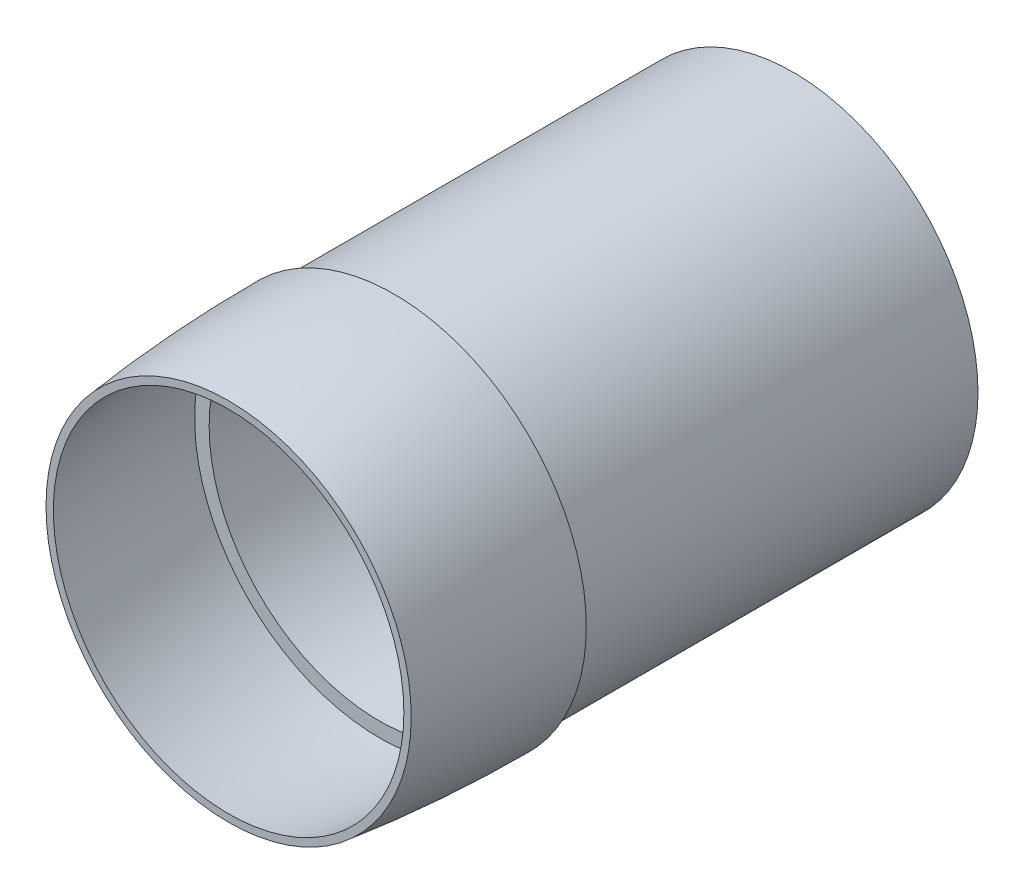
SolidWorks part; units mm, degrees
ref_plane "Front Plane" through (0, 0, 0) normal (0, 0, 1) x (1, 0, 0)
ref_plane "Top Plane" through (0, 0, 0) normal (0, 1, 0) x (1, 0, 0)
ref_plane "Right Plane" through (0, 0, 0) normal (1, 0, 0) x (0, 0, -1)
sketch "Sketch1" plane through (0, 0, 0) normal (1, 0, 0) x (0, 0, -1)
  line L0 (0, 291.8902) -> (0, 293.3902)
  line L1 (0, 253.8902) -> (-144.0127, 253.8902) construction
  line L2 (0, 0) -> (0, 253.8902) construction
  line L3 (0, 291.8902) -> (82, 291.8902)
  line L4 (82, 291.8902) -> (82, 253.8902)
  line L5 (0, 253.8902) -> (82, 253.8902) construction
  line L6 (79, 288.8902) -> (79, 253.8902)
  line L7 (-3, 288.8902) -> (79, 288.8902)
  line L8 (-3, 288.8902) -> (-3, 291.8748)
  line L10 (79, 253.8902) -> (82, 253.8902)
  line L11 (-34, 289.9033) -> (-34, 291.4135)
  line L12 (0, 291.8902) -> (0, 294.8902) construction
  arc A1 (-3, 291.8748) -> (-34, 289.9033) centre (0, 0) ccw
  arc A2 (-3, 291.8748) -> (-148.474, 251.3073) centre (0, 0) ccw construction
  arc A6 (0, 294.8902) -> (-150, 253.8902) centre (0, 0) ccw construction
  arc A8 (0, 293.3902) -> (-34, 291.4135) centre (0, 0) ccw
  dimension "D5" = 82
  dimension "D4" = 3
revolve "Revolve1" add sketch "Sketch1" angle 360 about L10
